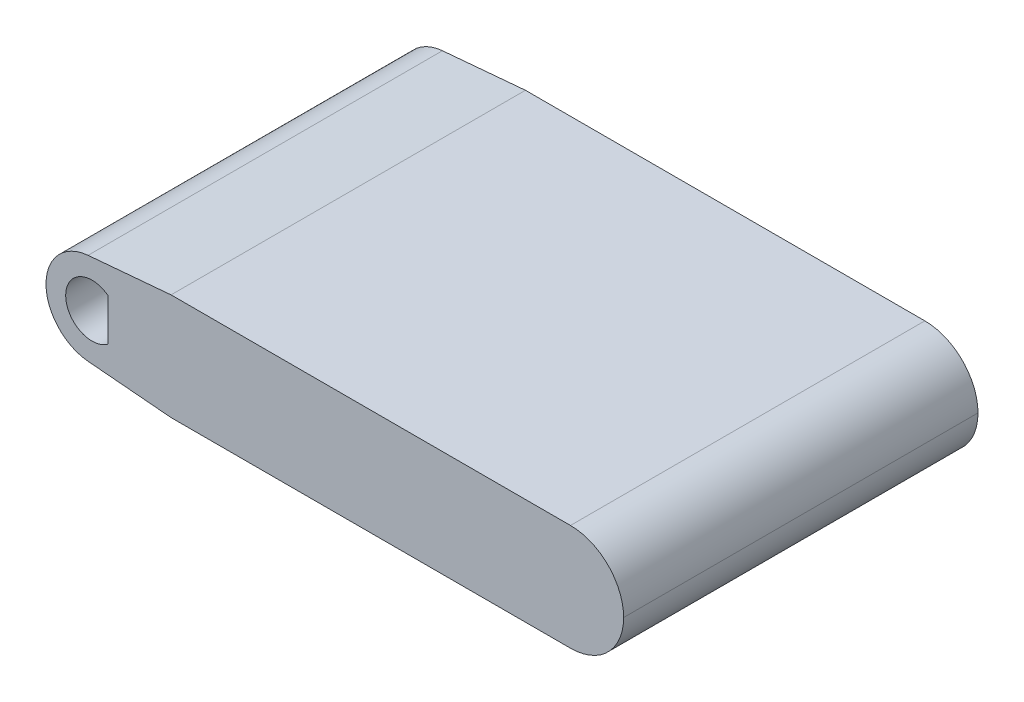
SolidWorks part; units mm, degrees
material "PBT General Purpose"
ref_plane "Front Plane" through (0, 0, 0) normal (0, 0, 1) x (1, 0, 0)
ref_plane "Top Plane" through (0, 0, 0) normal (0, 1, 0) x (1, 0, 0)
ref_plane "Right Plane" through (0, 0, 0) normal (1, 0, 0) x (0, 0, -1)
sketch "Sketch1" plane through (0, 0, 0) normal (0, 0, 1) x (1, 0, 0)
  line L4 (60, 6) -> (-6, 6)
  line L5 (-6, 6) -> (-6, -6)
  line L6 (0, 0) -> (-6, 0) construction
  line L7 (-6, -6) -> (60, -6)
  line L8 (60, -6) -> (60, 6)
  circle A0 centre (0, 0) radius 2.98
  dimension "D1" = 5.96
  dimension "D2" = 12
  dimension "D3" = 60
  dimension "D6" = 6
extrude "Boss-Extrude1" add sketch "Sketch1" along normal mid plane 40
fillet "Fillet2" radius 6 4 edges at (60, -6, 0) (60, 6, 0) (-6, -6, 0) (-6, 6, 0)
sketch "Sketch2" plane through (0, 0, -20) normal (0, 0, -1) x (-1, 0, 0)
  line L0 (1.8, -2.375) -> (1.8, 2.375) construction
  line L1 (0, 0) -> (0, 2.375) construction
  line L2 (-1.8, -2.375) -> (-1.8, 2.375)
  circle A0 centre (0, 0) radius 2.98 construction
  arc A1 (1.8, -2.375) -> (1.8, 2.375) centre (0, 0) ccw construction
  arc A2 (-1.8, -2.375) -> (-1.8, 2.375) centre (0, 0) cw
  dimension "D1" = 1.8
extrude "Boss-Extrude2" add sketch "Sketch2" against normal up to surface (40 mm away) up to face at (27, 0, 20)
sketch "Sketch4" plane through (0, 0, -20) normal (0, 0, -1) x (-1, 0, 0)
  line L0 (-8.917, 6) -> (0.4532, 5.1802)
  line L1 (-54, 6) -> (0, 6) construction
  line L2 (0.4532, -5.1802) -> (-8.917, -6)
  line L3 (0, -6) -> (-54, -6) construction
  line L4 (-8.917, 6) -> (-4.8925, 10.0245)
  line L5 (-4.8925, 10.0245) -> (10.6675, 8.3392)
  line L6 (10.6675, 8.3392) -> (9.2779, -7.5432)
  line L7 (9.2779, -7.5432) -> (-7.3921, -7.5432)
  line L8 (-7.3921, -7.5432) -> (-8.917, -6)
  arc A0 (0.4532, 5.1802) -> (0.4532, -5.1802) centre (0, 0) cw
  arc A1 (-1.8, -2.375) -> (-1.8, 2.375) centre (0, 0) ccw construction
  dimension "D1" = 5.2
  dimension "D2" = 5
extrude "Cut-Extrude1" cut sketch "Sketch4" against normal through all
